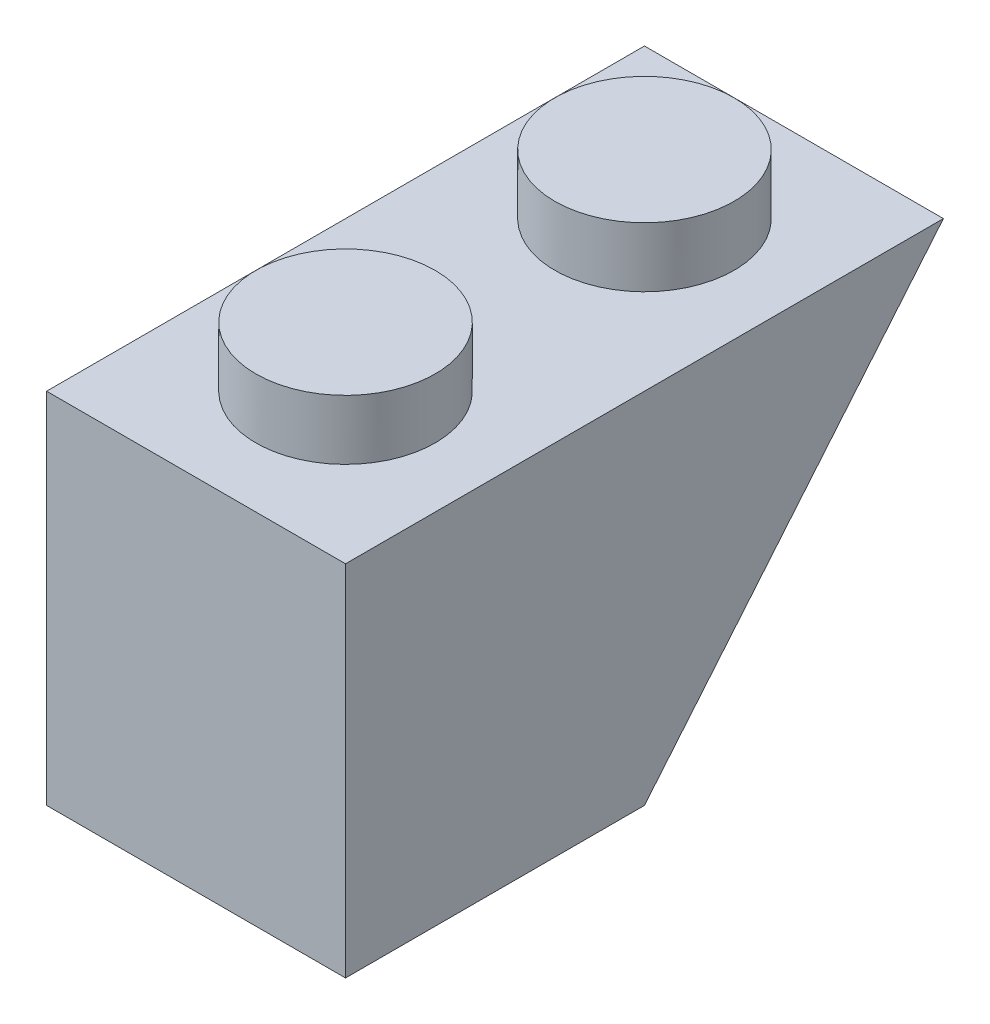
SolidWorks part; units mm, degrees
ref_plane "Front Plane" through (0, 0, 0) normal (0, 0, 1) x (1, 0, 0)
ref_plane "Top Plane" through (0, 0, 0) normal (0, 1, 0) x (1, 0, 0)
ref_plane "Right Plane" through (0, 0, 0) normal (1, 0, 0) x (0, 0, -1)
sketch "Sketch1" plane through (0, 0, 0) normal (1, 0, 0) x (0, 0, -1)
  line L0 (0, 0) -> (8, 0)
  line L1 (8, 0) -> (16, 9.6)
  line L2 (16, 9.6) -> (0, 9.6)
  line L3 (0, 9.6) -> (0, 0)
  dimension "D1" = 8
  dimension "D2" = 16
  dimension "D3" = 9.6
extrude "Boss-Extrude1" add sketch "Sketch1" along normal blind 8
sketch "Sketch2" plane through (0, 9.6, 0) normal (0, 1, 0) x (1, 0, 0)
  line L0 (4, 0) -> (4, 4) construction
  line L1 (8, 0) -> (0, 0) construction
  circle A0 centre (4, 4) radius 2.4
  dimension "D2" = 4.8
  dimension "D1" = 4
extrude "Boss-Extrude2" add sketch "Sketch2" along normal blind 1.6
pattern_linear "LPattern1" count 2 spacing 8 along (0, 0, -1) of "Boss-Extrude2"
shell "Shell1" thickness 1.6 removed face at (4, 0, -4)
